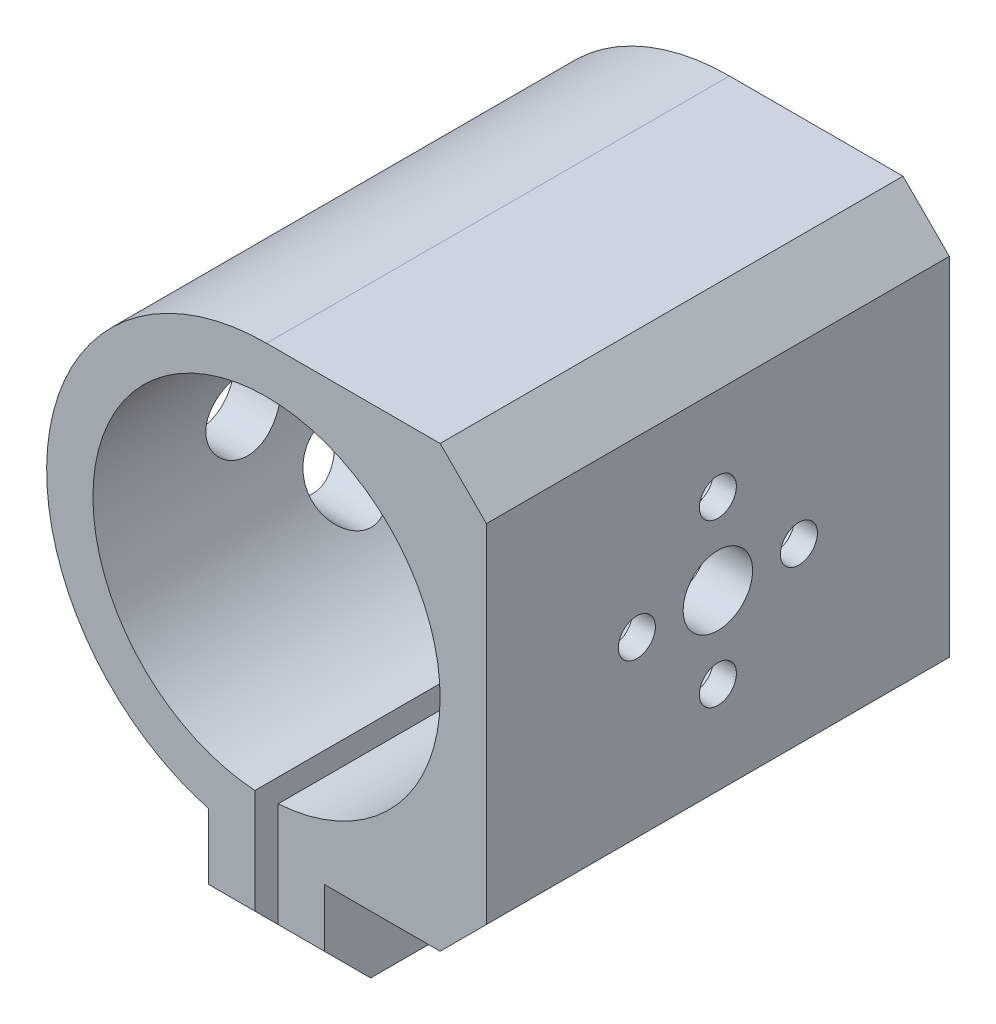
SolidWorks part; units mm, degrees
material "ABS"
ref_plane "前基準面" through (0, 0, 0) normal (0, 0, 1) x (1, 0, 0)
ref_plane "上基準面" through (0, 0, 0) normal (0, 1, 0) x (1, 0, 0)
ref_plane "右基準面" through (0, 0, 0) normal (1, 0, 0) x (0, 0, -1)
sketch "草圖1" plane through (0, 0, 0) normal (0, 0, 1) x (1, 0, 0)
  line L0 (0, 19) -> (19, 19)
  line L1 (19, 19) -> (19, -19)
  line L2 (19, -19) -> (0, -19)
  arc A0 (0, 19) -> (0, -19) centre (0, 0) ccw
  dimension "D1" = 19
  dimension "D2" = 38
  dimension "D3" = 19
extrude "填料-伸長1" add sketch "草圖1" along normal blind 40
sketch "草圖2" plane through (0, 0, 40) normal (0, 0, 1) x (1, 0, 0)
  line L1 (-5, -28) -> (5, -28)
  line L2 (-5, -28) -> (-5, 0)
  line L3 (-5, 0) -> (5, 0)
  line L4 (5, -28) -> (5, 0)
  line L5 (-5, -28) -> (5, 0) construction
  line L6 (-5, 0) -> (5, -28) construction
  point P0 (0, -14)
  point P5 (0, 0)
  dimension "D1" = 28
  dimension "D2" = 10
extrude "填料-伸長2" add sketch "草圖2" against normal blind 15
sketch "草圖3" plane through (0, 0, 40) normal (0, 0, 1) x (1, 0, 0)
  circle A0 centre (0, 0) radius 15
  dimension "D1" = 30
extrude "除料-伸長1" cut sketch "草圖3" against normal up to next
sketch "草圖4" plane through (0, 0, 0) normal (0, 0, -1) x (-1, 0, 0)
  line L1 (-7, 16) -> (7, 16)
  line L2 (-7, 16) -> (-7, 12)
  line L3 (-7, 12) -> (7, 12)
  line L4 (7, 16) -> (7, 12)
  point P4 (0, 16)
  dimension "D1" = 14
  dimension "D2" = 16
  dimension "D3" = 4
extrude "除料-伸長2" cut sketch "草圖4" against normal blind 20
sketch "草圖5" plane through (0, 0, 0) normal (0, 0, -1) x (-1, 0, 0)
  line L1 (-1, -30) -> (1, -30)
  line L2 (-1, -30) -> (-1, 0)
  line L3 (-1, 0) -> (1, 0)
  line L4 (1, -30) -> (1, 0)
  line L5 (-1, -30) -> (1, 0) construction
  line L6 (-1, 0) -> (1, -30) construction
  point P0 (0, -15)
  point P5 (0, 0)
  dimension "D1" = 2
  dimension "D2" = 30
extrude "除料-伸長3" cut sketch "草圖5" against normal up to next
sketch "草圖6" plane through (0, -19, 0) normal (0, -1, 0) x (-1, 0, 0)
  line L0 (0, -40) -> (19, -40) construction
  circle A0 centre (0, -6) radius 11
  point P4 (0, 0)
  point P5 (0, 0)
  dimension "D1" = 22
  dimension "D2" = 34
  dimension "D3" = 18.925
extrude "除料-伸長4" cut sketch "草圖6" against normal blind 20
sketch "草圖7" plane through (19, 0, 0) normal (1, 0, 0) x (0, 0, -1)
  line L0 (-40, 19) -> (0, 19) construction
  line L1 (0, -19) -> (0, 19) construction
  circle A0 centre (-20, 0) radius 3
  point P2 (0, 0)
  point P5 (-20, 19)
  point P6 (0, 0)
  point P9 (0, 0)
  dimension "D1" = 6
extrude "除料-伸長5" cut sketch "草圖7" against normal through all
ref_plane "平面1" through (17, 0, 0) normal (1, 0, 0) x (0, 0, -1)
sketch "草圖14" plane through (19, 0, 0) normal (1, 0, 0) x (0, 0, -1)
  line L0 (-40, 19) -> (0, 19) construction
  circle A0 centre (-20, 7) radius 1.6
  circle A1 centre (-20, 0) radius 3 construction
  point P4 (0, 0)
  point P7 (-20, 19)
  dimension "D1" = 3.2
  dimension "D2" = 7
extrude "除料-伸長6" cut sketch "草圖14" against normal blind 10
sketch "草圖15" plane through (17, 0, 0) normal (1, 0, 0) x (0, 0, -1)
  circle A0 centre (-20, 7) radius 3.25
  dimension "D1" = 6.5
extrude "除料-伸長7" cut sketch "草圖15" against normal through all
pattern_circular "環狀複製排列1" count 4 over 360 about axis through (-19, 0, 20) along (1, 0, 0) of "除料-伸長7", "除料-伸長6" reverse direction yes
chamfer "導角1" distance 4 angle 45 6 edges at (19, -19, 20) (19, 19, 20) (3, -28, 25) (-3, -28, 25) (-3, -28, 40) (3, -28, 40)
sketch "草圖16" plane through (-5, 0, 0) normal (-1, 0, 0) x (0, 0, 1)
  line L0 (29, -28) -> (36, -28) construction
  line L2 (29, -28) -> (36, -28) construction
  circle A0 centre (32.5, -23) radius 2.25
  point P2 (0, 0)
  point P5 (32.5, -28)
  point P6 (0, 0)
  point P10 (0, 0)
  dimension "D1" = 4.5
  dimension "D2" = 5
extrude "除料-伸長8" cut sketch "草圖16" against normal through all
sketch "草圖17" plane through (0, -19, 0) normal (0, -1, 0) x (-1, 0, 0)
  line L0 (-11, 6.2) -> (11, 6.2)
  line L1 (-11, 6.2) -> (-11, -6.2)
  line L2 (11, 6.2) -> (11, -6.2)
  line L3 (-11, -6.2) -> (11, -6.2)
  line L4 (-11, 6.2) -> (11, -6.2) construction
  line L5 (11, 6.2) -> (-11, -6.2) construction
  point P1 (0, 0)
  dimension "D1" = 22
  dimension "D2" = 12.4
extrude "除料-伸長10" cut sketch "草圖17" against normal blind 10
